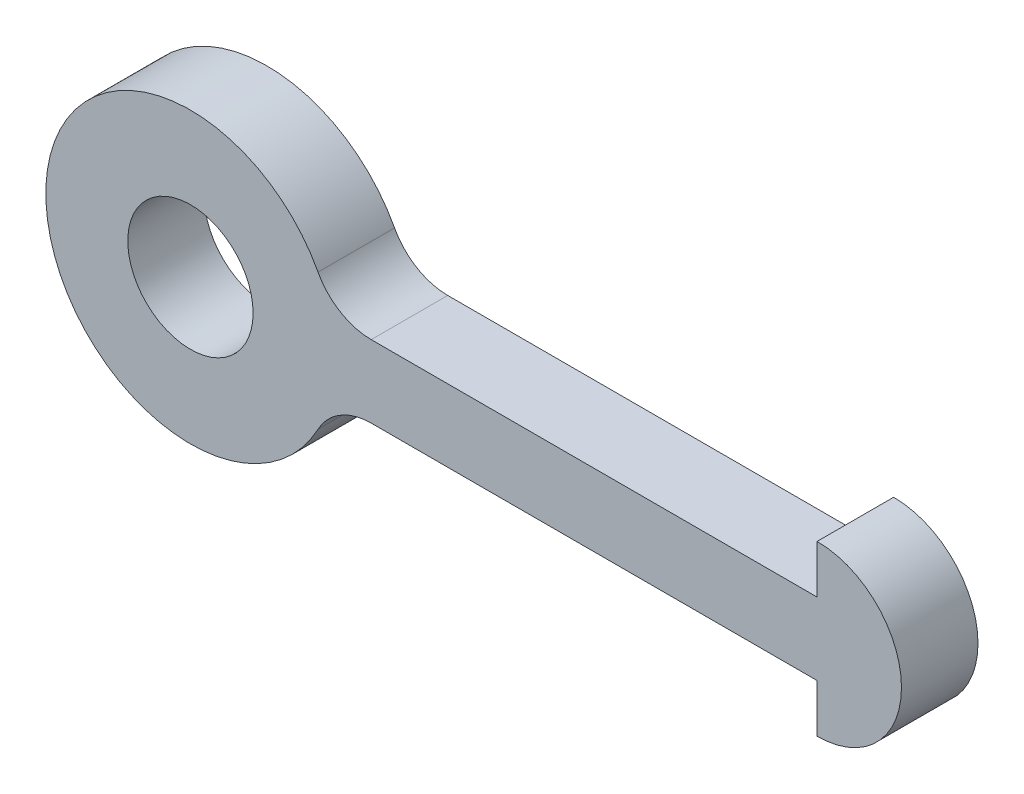
SolidWorks part; units mm, degrees
ref_plane "Front Plane" through (0, 0, 0) normal (0, 0, 1) x (1, 0, 0)
ref_plane "Top Plane" through (0, 0, 0) normal (0, 1, 0) x (1, 0, 0)
ref_plane "Right Plane" through (0, 0, 0) normal (1, 0, 0) x (0, 0, -1)
sketch "Sketch2" plane through (0, 0, 0) normal (0, 0, 1) x (1, 0, 0)
  line L0 (10, 3.5) -> (10, -3.5)
  line L1 (-10, -1.5) -> (10, -1.5)
  line L2 (-10, -1.5) -> (-10, 1.5)
  line L3 (-10, 1.5) -> (10, 1.5)
  line L4 (10, -1.5) -> (10, 1.5)
  line L5 (-10, -1.5) -> (10, 1.5) construction
  line L6 (-10, 1.5) -> (10, -1.5) construction
  line L7 (0, 0) -> (-32, 0) construction
  arc A2 (10, -3.5) -> (10, 3.5) centre (10, 0) ccw
  point P0 (0, 0)
  dimension "D3" = 3.5
  dimension "D1" = 3
  dimension "D2" = 20
extrude "Boss-Extrude1" add sketch "Sketch2" along normal mid plane 3.175 contours L0 A2 | L3 L2 L1 L0 region at (11.4854, 0, 0) region at (0, 0, 0)
sketch "Sketch3" plane through (0, 0, 1.5875) normal (0, 0, 1) x (1, 0, 0)
  line L0 (0, 0) -> (-19.9242, 0) construction
  line L1 (-10, -1.5) -> (-10, 1.5) construction
  circle A0 centre (-16, 0) radius 6
  dimension "D1" = 12
extrude "Boss-Extrude2" add sketch "Sketch3" against normal blind 3.175 separate body
sketch "Sketch4" plane through (0, 0, 1.5875) normal (0, 0, 1) x (1, 0, 0)
  circle A0 centre (-16, 0) radius 2.6
  circle A1 centre (-16, 0) radius 6 construction
  dimension "D1" = 5.2
extrude "Cut-Extrude1" cut sketch "Sketch4" against normal through all
sketch "Sketch6" plane through (0, 0, 1.5875) normal (0, 0, 1) x (1, 0, 0)
  line L0 (-10, 1.5) -> (-10.1905, 1.5)
  line L1 (-10.1905, 1.5) -> (-10, 0)
  line L2 (-10, -1.5) -> (-10, 1.5)
  line L3 (11.4203, 0) -> (-16.5833, 0) construction
  line L4 (-10.1905, -1.5) -> (-10, 0)
  line L5 (-10, -1.5) -> (-10.1905, -1.5)
  circle A0 centre (-16, 0) radius 6 construction
  line M7 (-10, 1.5) -> (-10, -1.5)
extrude "Boss-Extrude3" add sketch "Sketch6" against normal blind 3.175 contours L5 L4 M7 region at (-10.0635, -1, 1.5875)
mirror "Mirror1" about plane through (0, 0, 0) normal (0, 1, 0) of "Boss-Extrude3"
fillet "Fillet1" radius 2.5 2 edges at (-10.1905, -1.5, 0) (-10.1905, 1.5, 0)
ref_axis "Axis1" through (15.275, 0, 0) along (-1, 0, 0)
